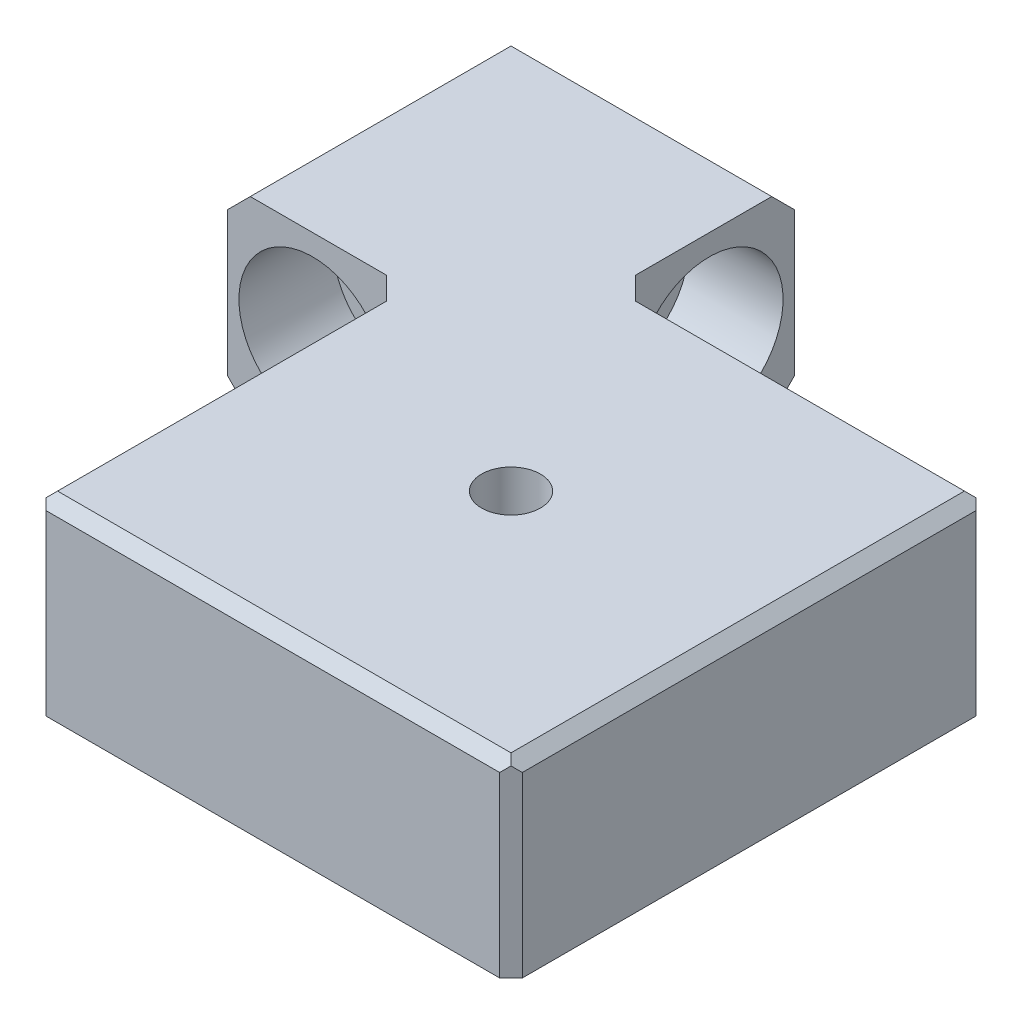
SolidWorks part; units mm, degrees
ref_plane "Front Plane" through (0, 0, 0) normal (0, 0, 1) x (1, 0, 0)
ref_plane "Top Plane" through (0, 0, 0) normal (0, 1, 0) x (1, 0, 0)
ref_plane "Right Plane" through (0, 0, 0) normal (1, 0, 0) x (0, 0, -1)
sketch "Sketch1" plane through (0, 0, 0) normal (0, 1, 0) x (1, 0, 0)
  line L1 (7.5, -5) -> (-7.5, -5)
  line L2 (7.5, -5) -> (7.5, 5)
  line L3 (7.5, 5) -> (-7.5, 5)
  line L4 (-7.5, -5) -> (-7.5, 5)
  line L5 (7.5, -5) -> (-7.5, 5) construction
  line L6 (7.5, 5) -> (-7.5, -5) construction
  line L8 (-7.5, 5) -> (-7.5, 20)
  line L9 (-7.5, 20) -> (7.5, 20)
  line L10 (7.5, 5) -> (7.5, 20)
  line L11 (7.5, 5) -> (17.5, 5)
  line L13 (7.5, 20) -> (17.5, 20)
  line L14 (17.5, 5) -> (17.5, 20)
  point P0 (0, 0)
  dimension "D1" = 10
  dimension "D2" = 15
  dimension "D3" = 15
  dimension "D4" = 10
extrude "Boss-Extrude1" add sketch "Sketch1" along normal blind 16.7 contours L4 L1 L2 L3 | L3 L10 L9 L8 | L11 L14 L13 L10 region at (0, 0, 0) region at (0, 0, -12.5) region at (12.5, 0, -12.5)
sketch "Sketch2" plane through (0, 0, 5) normal (0, 0, 1) x (1, 0, 0)
  line L0 (0, 0) -> (0, 16.7) construction
  line L1 (7.5, 0) -> (-7.5, 0) construction
  line L2 (7.5, 16.7) -> (-7.5, 16.7) construction
  circle A0 centre (0, 8.35) radius 6.5
  dimension "D1" = 13
extrude "Cut-Extrude1" cut sketch "Sketch2" against normal offset from surface (8.3 mm away) 16.7 up to face at (5, 8.35, -20)
sketch "Sketch3" plane through (17.5, 0, 0) normal (1, 0, 0) x (0, 0, -1)
  line L0 (12.5, 0) -> (12.5, 16.7) construction
  line L1 (5, 0) -> (20, 0) construction
  line L2 (5, 16.7) -> (20, 16.7) construction
  circle A0 centre (12.5, 8.35) radius 6.5
  dimension "D1" = 13
extrude "Cut-Extrude2" cut sketch "Sketch3" against normal offset from surface (8.3 mm away) 16.7 up to face at (-7.5, 8.35, -7.5)
sketch "Sketch4" plane through (0, 0, 0) normal (0, -1, 0) x (1, 0, 0)
  line L0 (0, 5) -> (0, -20) construction
  line L1 (7.5, 5) -> (-7.5, 5) construction
  line L2 (-7.5, -20) -> (17.5, -20) construction
  line L3 (17.5, -12.5) -> (-7.5, -12.5) construction
  line L4 (17.5, -5) -> (17.5, -20) construction
  line L5 (-7.5, 5) -> (-7.5, -20) construction
  circle A0 centre (0, -12.5) radius 6.5
  dimension "D1" = 13
extrude "Cut-Extrude3" cut sketch "Sketch4" against normal offset from surface (14.7 mm away) 2 up to face at (5.8333, 16.7, -6.6667)
fillet "Fillet8" radius 2 5 edges at (-7.5, 8.35, -20) (-7.5, 0, -7.5) (-7.5, 16.7, -7.5) (5, 16.7, -20) (5, 0, -20) profile chamfer
sketch "Sketch5" plane through (0, 16.7, 0) normal (0, 1, 0) x (1, 0, 0)
  line L1 (7.5, -37) -> (49.5, -37)
  line L2 (7.5, -37) -> (7.5, 5)
  line L3 (7.5, 5) -> (49.5, 5)
  line L4 (49.5, -37) -> (49.5, 5)
  line L6 (7.5, -16) -> (49.5, -16) construction
  line L7 (28.5, 5) -> (28.5, -37) construction
  line L8 (29.5, -17) -> (27.5, -17)
  line L9 (29.5, -17) -> (29.5, -15)
  circle A4 centre (28.5, -16) radius 2.6
  point P14 (28.5, 0)
  point P15 (12.5, -16)
  point P17 (28.5, -17)
  point P18 (29.5, -16)
  line M12 (7.5, -5) -> (7.5, 5)
  line M14 (7.5, 5) -> (17.5, 5)
  dimension "D8" = 5.2
  dimension "D1" = 42
  dimension "D2" = 42
extrude "Boss-Extrude3" add sketch "Sketch5" against normal up to surface (16.7 mm away) contours L1 L4 L3 L2 L9 L8 M14 M12 | L8 L9 region at (8.094, 16.7, 21) up to face at (6.8683, 0, -5.6317)
fillet "Fillet9" radius 1 5 edges at (7.5, 8.35, 5) (17.5, 8.35, -5) (7.5, 8.35, 37) (49.5, 8.35, 37) (49.5, 8.35, -5) profile chamfer
chamfer "Chamfer1" distance 1 angle 45 4 edges at (7.5, 16.7, 21) (28.5, 16.7, 37) (49.5, 16.7, 16) (33.5, 16.7, -5)
